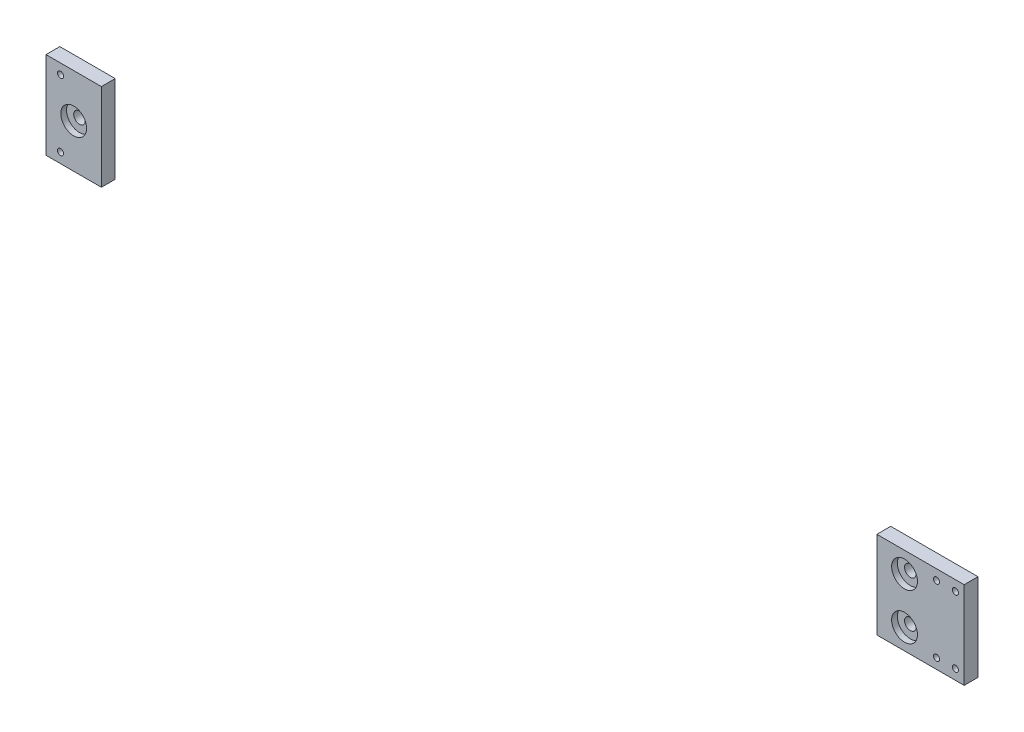
SolidWorks part; units mm, degrees
other "Front Bracket"
other "Rear Bracket"
ref_plane "Front Plane" through (0, 0, 0) normal (0, 0, 1) x (1, 0, 0)
ref_plane "Top Plane" through (0, 0, 0) normal (0, 1, 0) x (1, 0, 0)
ref_plane "Right Plane" through (0, 0, 0) normal (1, 0, 0) x (0, 0, -1)
sketch "Sketch2" plane through (0, 0, 0) normal (0, 0, 1) x (1, 0, 0)
  line L0 (304.725, 30) -> (276.237, 30)
  line L1 (-295.275, -30) -> (-257.175, -30)
  line L2 (-295.275, -30) -> (-295.275, 30)
  line L3 (-295.275, 30) -> (-257.175, 30)
  line L4 (-257.175, -30) -> (-257.175, 30)
  line L5 (-295.275, -30) -> (-257.175, 30) construction
  line L6 (-295.275, 30) -> (-257.175, -30) construction
  line L7 (304.725, -30) -> (342.825, -30)
  line L8 (304.725, -30) -> (304.725, 30) construction
  line L9 (304.725, 30) -> (342.825, 30)
  line L10 (342.825, -30) -> (342.825, 30)
  line L11 (304.725, -30) -> (342.825, 30) construction
  line L12 (304.725, 30) -> (342.825, -30) construction
  line L13 (276.237, -152.388) -> (276.237, 152.412) construction
  line L14 (276.237, 30) -> (276.237, -30)
  line L15 (276.237, -30) -> (304.725, -30)
  circle A0 centre (-276.225, 0) radius 3.9688
  circle A1 centre (-276.225, 0) radius 8.89
  circle A2 centre (323.775, 0) radius 3.9688 construction
  circle A3 centre (323.775, 0) radius 8.89 construction
  point P0 (-276.225, 0)
  point P9 (323.775, 0)
  dimension "D3" = 17.78
  dimension "D4" = 7.9375
  dimension "D1" = 38.1
  dimension "D2" = 60
  dimension "D6" = 600
  dimension "D5" = 2
extrude "Main Extrusion" add sketch "Sketch2" along normal blind 5.5575 contours L1 L4 L3 L2 A1 | A1 A0 | L7 L10 L9 L8 A3 | A3 A2 region at (309.531, 0, 0) region at (-294.5643, 0, 0) region at (-284.8636, 0, 0)
extrude "Counterbore extrusion" add sketch "Sketch2<3>" along normal blind 9.525 contours L1 L4 L3 L2 A1 | L7 L10 L9 L8 A3 region at (309.531, 0, 0) region at (-294.5643, 0, 0)
sketch "Sketch2<3>" plane through (0, 0, 0) normal (0, 0, 1) x (1, 0, 0) same geometry as "Sketch2"
sketch "Sketch3" plane through (0, 0, 9.525) normal (0, 0, 1) x (1, 0, 0)
  line L0 (-295.275, 0) -> (-257.175, 0) construction
  line L2 (-257.175, -30) -> (-257.175, 30) construction
  circle A0 centre (-285.275, 23) radius 2.1
  circle A1 centre (-285.275, -23) radius 2.1
  point P6 (-276.225, 0)
  dimension "D1" = 4.2
  dimension "D2" = 46
  dimension "D3" = 10
extrude "M5 Threaded holse for front bracket" cut sketch "Sketch3" against normal up to surface (9.525 mm away) up to face at (-272.2562, 0, 0)
sketch "Sketch5" plane through (0, 0, 9.525) normal (0, 0, 1) x (1, 0, 0)
  line L0 (317.275, 23) -> (330.275, 23) construction
  line L1 (317.275, 23) -> (317.275, -23) construction
  circle A0 centre (317.275, 23) radius 2.1
  circle A1 centre (330.275, 23) radius 2.1
  circle A2 centre (330.275, -23) radius 2.1
  circle A3 centre (317.275, -23) radius 2.1
  point P0 (323.775, 0)
  point P5 (323.775, 23)
  point P6 (317.275, 0)
  dimension "D6" = 4.2
  dimension "D3" = 90
  dimension "D4" = 13
  dimension "D5" = 46
  dimension "D1" = 2
  dimension "D2" = 2
extrude "M5 Threaded holes for bracket" cut sketch "Sketch5" against normal up to surface (9.525 mm away) up to face at (309.531, 0, 0)
sketch "Sketch6" plane through (0, 0, 9.525) normal (0, 0, 1) x (1, 0, 0)
  line L0 (295.275, -171.45) -> (295.275, 171.45) construction
  line L1 (295.275, -171.45) -> (295.275, 171.45) construction
  line L2 (13.75, 0) -> (-13.75, 0) construction
  circle A0 centre (295.275, 15.875) radius 8.89
  circle A1 centre (295.275, 15.875) radius 3.9688
  circle A2 centre (323.775, 0) radius 8.89 construction
  circle A3 centre (323.775, 0) radius 3.9688 construction
  circle A4 centre (295.275, -15.875) radius 3.9688
  circle A5 centre (295.275, -15.875) radius 8.89
  dimension "D1" = 31.75
extrude "centre bore" cut sketch "Sketch6" against normal through all contours L1 A1 | A1 L1 | L1 A4 | A4 L1 region at (293.5906, -15.875, 9.525) region at (296.9594, -15.875, 9.525) region at (293.5906, 15.875, 9.525) region at (296.9594, 15.875, 9.525)
extrude "counterbore" cut sketch "Sketch6<3>" against normal offset from surface (3.9675 mm away) 5.5575 up to face at (309.531, 0, 0)
sketch "Sketch6<3>" plane through (0, 0, 9.525) normal (0, 0, 1) x (1, 0, 0) same geometry as "Sketch6"
sketch "Sketch7" plane through (0, 0, 9.525) normal (0, 0, 1) x (1, 0, 0)
  line L1 (342.825, 30) -> (336.275, 30)
  line L2 (342.825, 30) -> (342.825, -30)
  line L3 (342.825, -30) -> (336.275, -30)
  line L4 (336.275, 30) -> (336.275, -30)
extrude "stupid cut" cut sketch "Sketch7" against normal through all
